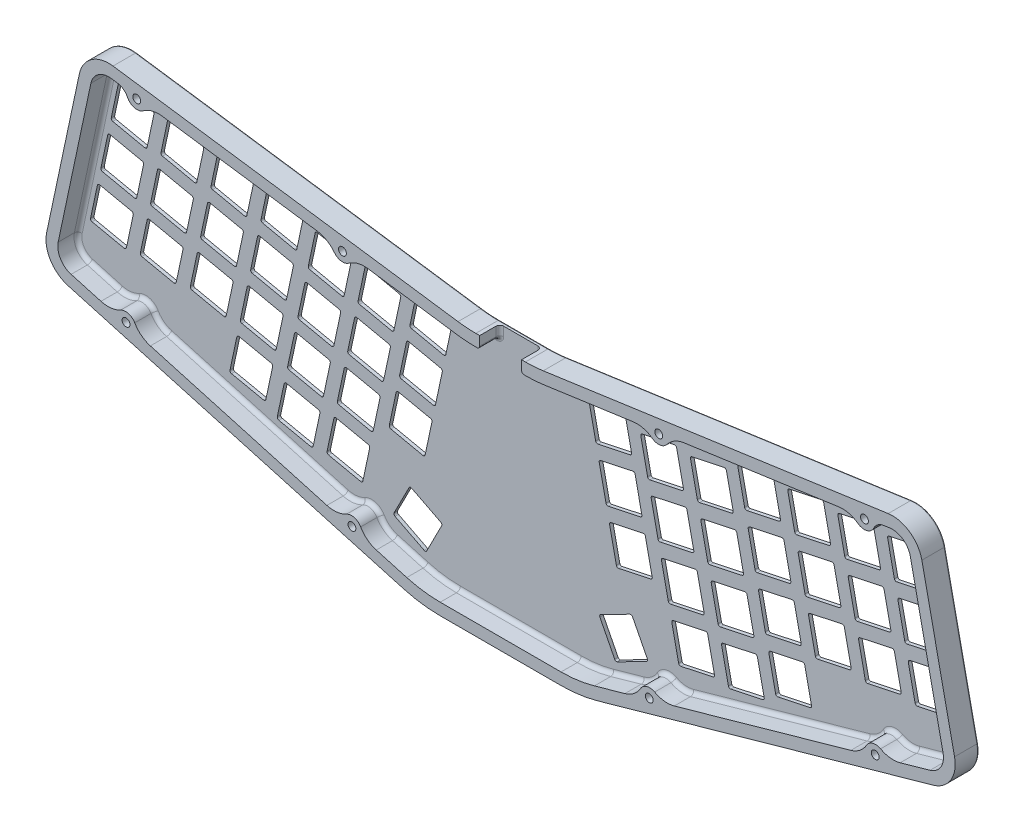
SolidWorks part; units mm, degrees
ref_plane "Front Plane" through (0, 0, 0) normal (0, 0, 1) x (1, 0, 0)
ref_plane "Top Plane" through (0, 0, 0) normal (0, 1, 0) x (1, 0, 0)
ref_plane "Right Plane" through (0, 0, 0) normal (1, 0, 0) x (0, 0, -1)
sketch "Model" plane through (0, 0, 0) normal (0, 0, 1) x (1, 0, 0)
  line L0 (7.1929, 63.9009) -> (19.4198, 61.302)
  line L1 (19.9974, 60.4125) -> (17.3986, 48.1856)
  line L2 (16.509, 47.6079) -> (4.2822, 50.2068)
  line L3 (3.7045, 51.0964) -> (6.3034, 63.3232)
  line L4 (3.2426, 45.3161) -> (15.4694, 42.7172)
  line L5 (16.0471, 41.8276) -> (13.4482, 29.6008)
  line L6 (12.5587, 29.0231) -> (0.3318, 31.622)
  line L7 (-0.2458, 32.5116) -> (2.3531, 44.7384)
  line L8 (-0.7077, 26.7313) -> (11.5191, 24.1324)
  line L9 (12.0968, 23.2428) -> (9.4979, 11.016)
  line L10 (8.6084, 10.4383) -> (-3.6185, 13.0372)
  line L11 (-4.1962, 13.9268) -> (-1.5973, 26.1536)
  line L12 (26.1936, 61.9069) -> (38.4204, 59.308)
  line L13 (38.9981, 58.4184) -> (36.3992, 46.1916)
  line L14 (35.5096, 45.6139) -> (23.2828, 48.2128)
  line L15 (22.7051, 49.1023) -> (25.304, 61.3292)
  line L16 (22.2432, 43.3221) -> (34.4701, 40.7232)
  line L17 (35.0478, 39.8336) -> (32.4489, 27.6068)
  line L18 (31.5593, 27.0291) -> (19.3325, 29.628)
  line L19 (18.7548, 30.5175) -> (21.3537, 42.7444)
  line L20 (18.2929, 24.7373) -> (30.5198, 22.1384)
  line L21 (31.0974, 21.2488) -> (28.4985, 9.022)
  line L22 (27.609, 8.4443) -> (15.3821, 11.0432)
  line L23 (14.8045, 11.9327) -> (17.4034, 24.1596)
  line L24 (45.2981, 60.4019) -> (57.525, 57.803)
  line L25 (58.1027, 56.9135) -> (55.5038, 44.6866)
  line L26 (54.6142, 44.109) -> (42.3874, 46.7078)
  line L27 (41.8097, 47.5974) -> (44.4086, 59.8242)
  line L28 (41.3478, 41.8171) -> (53.5747, 39.2182)
  line L29 (54.1523, 38.3287) -> (51.5534, 26.1018)
  line L30 (50.6639, 25.5241) -> (38.4371, 28.123)
  line L31 (37.8594, 29.0126) -> (40.4583, 41.2394)
  line L32 (37.3975, 23.2323) -> (49.6243, 20.6334)
  line L33 (50.202, 19.7439) -> (47.6031, 7.517)
  line L34 (46.7136, 6.9393) -> (34.4867, 9.5382)
  line L35 (33.9091, 10.4278) -> (36.5079, 22.6546)
  line L36 (64.4027, 58.897) -> (76.6296, 56.2981)
  line L37 (77.2072, 55.4085) -> (74.6083, 43.1817)
  line L38 (73.7188, 42.604) -> (61.492, 45.2029)
  line L39 (60.9143, 46.0924) -> (63.5132, 58.3193)
  line L40 (60.4524, 40.3122) -> (72.6792, 37.7133)
  line L41 (73.2569, 36.8237) -> (70.658, 24.5969)
  line L42 (69.7685, 24.0192) -> (57.5416, 26.6181)
  line L43 (56.964, 27.5076) -> (59.5629, 39.7345)
  line L44 (56.5021, 21.7274) -> (68.7289, 19.1285)
  line L45 (69.3066, 18.2389) -> (66.7077, 6.0121)
  line L46 (65.8182, 5.4344) -> (53.5913, 8.0333)
  line L47 (53.0136, 8.9228) -> (55.6125, 21.1497)
  line L48 (52.5518, 3.1425) -> (64.7786, 0.5437)
  line L49 (65.3563, -0.3459) -> (62.7574, -12.5727)
  line L50 (61.8678, -13.1504) -> (49.641, -10.5515)
  line L51 (49.0633, -9.662) -> (51.6622, 2.5649)
  line L52 (82.4677, 52.5013) -> (94.6946, 49.9024)
  line L53 (95.2723, 49.0128) -> (92.6734, 36.786)
  line L54 (91.7838, 36.2083) -> (79.557, 38.8072)
  line L55 (78.9793, 39.6967) -> (81.5782, 51.9236)
  line L56 (78.5174, 33.9165) -> (90.7443, 31.3176)
  line L57 (91.3219, 30.428) -> (88.723, 18.2012)
  line L58 (87.8335, 17.6235) -> (75.6067, 20.2224)
  line L59 (75.029, 21.1119) -> (77.6279, 33.3388)
  line L60 (74.5671, 15.3317) -> (86.7939, 12.7328)
  line L61 (87.3716, 11.8432) -> (84.7727, -0.3836)
  line L62 (83.8832, -0.9613) -> (71.6563, 1.6376)
  line L63 (71.0787, 2.5271) -> (73.6776, 14.754)
  line L64 (101.4684, 50.5072) -> (113.6952, 47.9083)
  line L65 (114.2729, 47.0188) -> (111.674, 34.792)
  line L66 (110.7845, 34.2143) -> (98.5576, 36.8132)
  line L67 (97.9799, 37.7027) -> (100.5788, 49.9296)
  line L68 (97.5181, 31.9224) -> (109.7449, 29.3235)
  line L69 (110.3226, 28.434) -> (107.7237, 16.2072)
  line L70 (106.8341, 15.6295) -> (94.6073, 18.2284)
  line L71 (94.0296, 19.1179) -> (96.6285, 31.3448)
  line L72 (93.5677, 13.3376) -> (105.7946, 10.7387)
  line L73 (106.3723, 9.8492) -> (103.7734, -2.3777)
  line L74 (102.8838, -2.9553) -> (90.657, -0.3564)
  line L75 (90.0793, 0.5331) -> (92.6782, 12.76)
  line L76 (134.1052, 48.9374) -> (131.5063, 36.7105)
  line L77 (130.6167, 36.1328) -> (118.3899, 38.7317)
  line L78 (117.8122, 39.6213) -> (120.4111, 51.8481)
  line L79 (117.3503, 33.841) -> (129.5772, 31.2421)
  line L80 (130.1548, 30.3526) -> (127.556, 18.1257)
  line L81 (126.6664, 17.548) -> (114.4396, 20.1469)
  line L82 (113.8619, 21.0365) -> (116.4608, 33.2633)
  line L83 (113.4, 15.2562) -> (125.6268, 12.6573)
  line L84 (126.2045, 11.7678) -> (123.6056, -0.4591)
  line L85 (122.7161, -1.0368) -> (110.4892, 1.5621)
  line L86 (109.9116, 2.4517) -> (112.5105, 14.6785)
  line L87 (70.6168, -3.2531) -> (82.8436, -5.852)
  line L88 (83.4213, -6.7416) -> (80.8224, -18.9684)
  line L89 (79.9329, -19.5461) -> (67.706, -16.9472)
  line L90 (67.1283, -16.0577) -> (69.7272, -3.8308)
  line L91 (89.6174, -5.2472) -> (101.8443, -7.8461)
  line L92 (102.4219, -8.7356) -> (99.823, -20.9625)
  line L93 (98.9335, -21.5401) -> (86.7066, -18.9412)
  line L94 (86.129, -18.0517) -> (88.7279, -5.8248)
  line L95 (117.654, -29.3648) -> (112.0852, -26.5274)
  line L96 (111.7574, -25.5186) -> (117.4323, -14.381)
  line L97 (118.4411, -14.0533) -> (129.5787, -19.7282)
  line L98 (129.9064, -20.7369) -> (124.2315, -31.8745)
  line L99 (123.2228, -32.2023) -> (117.654, -29.3648)
  line L100 (112.629, -33.5493) -> (124.2783, -36.8388)
  line L101 (137.0504, -38.6074) -> (160.1264, -38.6074)
  line L102 (160.1264, -38.6074) -> (183.2025, -38.6074)
  line L103 (195.9746, -36.8388) -> (207.6239, -33.5493)
  line L104 (226.4824, -28.2242) -> (271.949, -15.3856)
  line L105 (271.949, -15.3856) -> (293.9202, -9.1816)
  line L106 (210.7632, 57.9332) -> (177.0346, 53.1572)
  line L107 (169.604, 52.6338) -> (150.6488, 52.6338)
  line L108 (143.2182, 53.1572) -> (109.4896, 57.9332)
  line L109 (90.0873, 60.6806) -> (30.9176, 69.0589)
  line L110 (289.3352, 69.0589) -> (230.1656, 60.6806)
  line L111 (26.3327, -9.1816) -> (48.3039, -15.3856)
  line L112 (48.3039, -15.3856) -> (93.7705, -28.2242)
  line L113 (312.7787, -3.8564) -> (324.1811, -0.6367)
  line L114 (-2.1254, 39.3007) -> (3.622, 66.34)
  line L115 (-2.1254, 39.3007) -> (-8.8731, 7.5553)
  line L116 (13.8071, 71.4818) -> (11.4504, 71.8155)
  line L117 (-3.9283, -0.6367) -> (7.4742, -3.8564)
  line L118 (306.4458, 71.4818) -> (308.8024, 71.8155)
  line L119 (322.3782, 39.3007) -> (329.1259, 7.5553)
  line L120 (322.3782, 39.3007) -> (316.6308, 66.34)
  line L121 (121.3006, 52.4258) -> (133.5275, 49.8269)
  line L122 (313.0599, 63.9009) -> (300.8331, 61.302)
  line L123 (300.2554, 60.4125) -> (302.8543, 48.1856)
  line L124 (303.7438, 47.6079) -> (315.9707, 50.2068)
  line L125 (316.5483, 51.0964) -> (313.9494, 63.3232)
  line L126 (317.0102, 45.3161) -> (304.7834, 42.7172)
  line L127 (304.2057, 41.8276) -> (306.8046, 29.6008)
  line L128 (307.6941, 29.0231) -> (319.921, 31.622)
  line L129 (320.4987, 32.5116) -> (317.8998, 44.7384)
  line L130 (320.9605, 26.7313) -> (308.7337, 24.1324)
  line L131 (308.156, 23.2428) -> (310.7549, 11.016)
  line L132 (311.6445, 10.4383) -> (323.8713, 13.0372)
  line L133 (324.449, 13.9268) -> (321.8501, 26.1536)
  line L134 (294.0593, 61.9069) -> (281.8324, 59.308)
  line L135 (281.2548, 58.4184) -> (283.8536, 46.1916)
  line L136 (284.7432, 45.6139) -> (296.97, 48.2128)
  line L137 (297.5477, 49.1023) -> (294.9488, 61.3292)
  line L138 (298.0096, 43.3221) -> (285.7828, 40.7232)
  line L139 (285.2051, 39.8336) -> (287.804, 27.6068)
  line L140 (288.6935, 27.0291) -> (300.9204, 29.628)
  line L141 (301.498, 30.5175) -> (298.8991, 42.7444)
  line L142 (301.9599, 24.7373) -> (289.7331, 22.1384)
  line L143 (289.1554, 21.2488) -> (291.7543, 9.022)
  line L144 (292.6438, 8.4443) -> (304.8707, 11.0432)
  line L145 (305.4484, 11.9327) -> (302.8495, 24.1596)
  line L146 (274.9547, 60.4019) -> (262.7278, 57.803)
  line L147 (262.1502, 56.9135) -> (264.7491, 44.6866)
  line L148 (265.6386, 44.109) -> (277.8655, 46.7078)
  line L149 (278.4431, 47.5974) -> (275.8442, 59.8242)
  line L150 (278.905, 41.8171) -> (266.6782, 39.2182)
  line L151 (266.1005, 38.3287) -> (268.6994, 26.1018)
  line L152 (269.5889, 25.5241) -> (281.8158, 28.123)
  line L153 (282.3935, 29.0126) -> (279.7946, 41.2394)
  line L154 (282.8553, 23.2323) -> (270.6285, 20.6334)
  line L155 (270.0508, 19.7439) -> (272.6497, 7.517)
  line L156 (273.5393, 6.9393) -> (285.7661, 9.5382)
  line L157 (286.3438, 10.4278) -> (283.7449, 22.6546)
  line L158 (255.8501, 58.897) -> (243.6233, 56.2981)
  line L159 (243.0456, 55.4085) -> (245.6445, 43.1817)
  line L160 (246.534, 42.604) -> (258.7609, 45.2029)
  line L161 (259.3385, 46.0924) -> (256.7397, 58.3193)
  line L162 (259.8004, 40.3122) -> (247.5736, 37.7133)
  line L163 (246.9959, 36.8237) -> (249.5948, 24.5969)
  line L164 (250.4843, 24.0192) -> (262.7112, 26.6181)
  line L165 (263.2889, 27.5076) -> (260.69, 39.7345)
  line L166 (263.7508, 21.7274) -> (251.5239, 19.1285)
  line L167 (250.9462, 18.2389) -> (253.5451, 6.0121)
  line L168 (254.4347, 5.4344) -> (266.6615, 8.0333)
  line L169 (267.2392, 8.9228) -> (264.6403, 21.1497)
  line L170 (267.7011, 3.1425) -> (255.4742, 0.5437)
  line L171 (254.8966, -0.3459) -> (257.4954, -12.5727)
  line L172 (258.385, -13.1504) -> (270.6118, -10.5515)
  line L173 (271.1895, -9.662) -> (268.5906, 2.5649)
  line L174 (237.7851, 52.5013) -> (225.5582, 49.9024)
  line L175 (224.9806, 49.0128) -> (227.5795, 36.786)
  line L176 (228.469, 36.2083) -> (240.6958, 38.8072)
  line L177 (241.2735, 39.6967) -> (238.6746, 51.9236)
  line L178 (241.7354, 33.9165) -> (229.5086, 31.3176)
  line L179 (228.9309, 30.428) -> (231.5298, 18.2012)
  line L180 (232.4193, 17.6235) -> (244.6462, 20.2224)
  line L181 (245.2238, 21.1119) -> (242.6249, 33.3388)
  line L182 (245.6857, 15.3317) -> (233.4589, 12.7328)
  line L183 (232.8812, 11.8432) -> (235.4801, -0.3836)
  line L184 (236.3696, -0.9613) -> (248.5965, 1.6376)
  line L185 (249.1742, 2.5271) -> (246.5753, 14.754)
  line L186 (218.7845, 50.5072) -> (206.5576, 47.9083)
  line L187 (205.9799, 47.0188) -> (208.5788, 34.792)
  line L188 (209.4684, 34.2143) -> (221.6952, 36.8132)
  line L189 (222.2729, 37.7027) -> (219.674, 49.9296)
  line L190 (222.7348, 31.9224) -> (210.5079, 29.3235)
  line L191 (209.9303, 28.434) -> (212.5292, 16.2072)
  line L192 (213.4187, 15.6295) -> (225.6455, 18.2284)
  line L193 (226.2232, 19.1179) -> (223.6243, 31.3448)
  line L194 (226.6851, 13.3376) -> (214.4583, 10.7387)
  line L195 (213.8806, 9.8492) -> (216.4795, -2.3777)
  line L196 (217.369, -2.9553) -> (229.5959, -0.3564)
  line L197 (230.1735, 0.5331) -> (227.5746, 12.76)
  line L198 (186.1477, 48.9374) -> (188.7466, 36.7105)
  line L199 (189.6361, 36.1328) -> (201.8629, 38.7317)
  line L200 (202.4406, 39.6213) -> (199.8417, 51.8481)
  line L201 (202.9025, 33.841) -> (190.6757, 31.2421)
  line L202 (190.098, 30.3526) -> (192.6969, 18.1257)
  line L203 (193.5864, 17.548) -> (205.8133, 20.1469)
  line L204 (206.3909, 21.0365) -> (203.792, 33.2633)
  line L205 (206.8528, 15.2562) -> (194.626, 12.6573)
  line L206 (194.0483, 11.7678) -> (196.6472, -0.4591)
  line L207 (197.5367, -1.0368) -> (209.7636, 1.5621)
  line L208 (210.3413, 2.4517) -> (207.7424, 14.6785)
  line L209 (249.636, -3.2531) -> (237.4092, -5.852)
  line L210 (236.8315, -6.7416) -> (239.4304, -18.9684)
  line L211 (240.32, -19.5461) -> (252.5468, -16.9472)
  line L212 (253.1245, -16.0577) -> (250.5256, -3.8308)
  line L213 (230.6354, -5.2472) -> (218.4086, -7.8461)
  line L214 (217.8309, -8.7356) -> (220.4298, -20.9625)
  line L215 (221.3193, -21.5401) -> (233.5462, -18.9412)
  line L216 (234.1239, -18.0517) -> (231.525, -5.8248)
  line L217 (202.5988, -29.3648) -> (208.1676, -26.5274)
  line L218 (208.4954, -25.5186) -> (202.8205, -14.381)
  line L219 (201.8118, -14.0533) -> (190.6742, -19.7282)
  line L220 (190.3464, -20.7369) -> (196.0213, -31.8745)
  line L221 (197.03, -32.2023) -> (202.5988, -29.3648)
  line L222 (198.9522, 52.4258) -> (186.7253, 49.8269)
  line L223 (169.604, 55.6338) -> (150.6488, 55.6338)
  line L224 (143.6388, 56.1276) -> (11.8711, 74.7858)
  line L225 (0.6876, 66.9637) -> (-5.0598, 39.9244)
  line L226 (-5.0598, 39.9244) -> (-11.8075, 8.179)
  line L227 (-4.7435, -3.5238) -> (47.4886, -18.2727)
  line L228 (47.4886, -18.2727) -> (123.463, -39.7259)
  line L229 (137.0504, -41.6074) -> (160.1264, -41.6074)
  line L230 (160.1264, -41.6074) -> (183.2025, -41.6074)
  line L231 (196.7898, -39.7259) -> (272.7642, -18.2727)
  line L232 (272.7642, -18.2727) -> (324.9963, -3.5238)
  line L233 (332.0603, 8.179) -> (325.3126, 39.9244)
  line L234 (325.3126, 39.9244) -> (319.5653, 66.9637)
  line L235 (308.3818, 74.7858) -> (176.614, 56.1276)
  line L236 (169.604, 57.1338) -> (150.6488, 57.1338)
  line L237 (143.8491, 57.6128) -> (12.0814, 76.271)
  line L238 (-0.7797, 67.2756) -> (-6.527, 40.2363)
  line L239 (-6.527, 40.2363) -> (-13.2747, 8.4909)
  line L240 (-5.1511, -4.9673) -> (47.081, -19.7163)
  line L241 (47.081, -19.7163) -> (123.0554, -41.1694)
  line L242 (137.0504, -43.1074) -> (160.1264, -43.1074)
  line L243 (160.1264, -43.1074) -> (183.2025, -43.1074)
  line L244 (197.1974, -41.1694) -> (273.1718, -19.7163)
  line L245 (273.1718, -19.7163) -> (325.404, -4.9673)
  line L246 (333.5276, 8.4909) -> (326.7799, 40.2363)
  line L247 (326.7799, 40.2363) -> (321.0325, 67.2756)
  line L248 (308.1715, 76.271) -> (176.4037, 57.6128)
  arc A0 (106.6702, -28.8979) -> (101.2821, -27.3764) centre (103.1997, -30.8868) ccw
  arc A1 (93.7705, -28.2242) -> (101.2821, -27.3764) centre (96.4879, -18.6005) ccw
  arc A2 (106.6702, -28.8979) -> (112.629, -33.5493) centre (115.3464, -23.9256) ccw
  circle A3 centre (103.3356, -30.4056) radius 1.5
  arc A4 (207.6239, -33.5493) -> (213.5826, -28.8979) centre (204.9064, -23.9256) ccw
  arc A5 (218.9708, -27.3764) -> (226.4824, -28.2242) centre (223.7649, -18.6005) ccw
  arc A6 (218.9708, -27.3764) -> (213.5826, -28.8979) centre (217.0531, -30.8868) ccw
  circle A7 centre (216.9173, -30.4056) radius 1.5
  arc A8 (218.0932, 56.0855) -> (223.6367, 56.8704) centre (220.4644, 59.3069) ccw
  arc A9 (96.6161, 56.8704) -> (102.1596, 56.0855) centre (99.7884, 59.3069) ccw
  arc A10 (109.4896, 57.9332) -> (102.1596, 56.0855) centre (108.0876, 48.032) ccw
  arc A11 (96.6161, 56.8704) -> (90.0873, 60.6806) centre (88.6852, 50.7793) ccw
  arc A12 (218.0932, 56.0855) -> (210.7632, 57.9332) centre (212.1652, 48.032) ccw
  arc A13 (230.1656, 60.6806) -> (223.6367, 56.8704) centre (231.5676, 50.7793) ccw
  circle A14 centre (99.7183, 58.8118) radius 1.5
  circle A15 centre (220.5345, 58.8118) radius 1.5
  arc A16 (305.2671, -3.0086) -> (299.8789, -4.5301) centre (303.3494, -6.519) ccw
  arc A17 (20.3739, -4.5301) -> (14.9858, -3.0086) centre (16.9034, -6.519) ccw
  arc A18 (20.3739, -4.5301) -> (26.3327, -9.1816) centre (29.0501, 0.4421) ccw
  arc A19 (305.2671, -3.0086) -> (312.7787, -3.8564) centre (310.0612, 5.7673) ccw
  arc A20 (293.9202, -9.1816) -> (299.8789, -4.5301) centre (291.2027, 0.4421) ccw
  arc A21 (7.4742, -3.8564) -> (14.9858, -3.0086) centre (10.1916, 5.7673) ccw
  circle A22 centre (17.0393, -6.0378) radius 1.5
  circle A23 centre (303.2135, -6.0378) radius 1.5
  arc A24 (-8.8731, 7.5553) -> (-3.9283, -0.6367) centre (-2.026, 6.0999) ccw
  arc A25 (11.4504, 71.8155) -> (3.622, 66.34) centre (10.469, 64.8846) ccw
  arc A26 (316.6308, 66.34) -> (308.8024, 71.8155) centre (309.7838, 64.8846) ccw
  arc A27 (324.1811, -0.6367) -> (329.1259, 7.5553) centre (322.2789, 6.0999) ccw
  arc A28 (296.6652, 67.2112) -> (302.641, 68.6986) centre (299.0364, 70.4326) ccw
  arc A29 (17.6118, 68.6986) -> (23.5876, 67.2112) centre (21.2165, 70.4326) ccw
  arc A30 (30.9176, 69.0589) -> (23.5876, 67.2112) centre (29.5156, 59.1577) ccw
  arc A31 (17.6118, 68.6986) -> (13.8071, 71.4818) centre (13.106, 66.5312) ccw
  arc A32 (306.4458, 71.4818) -> (302.641, 68.6986) centre (307.1468, 66.5312) ccw
  arc A33 (296.6652, 67.2112) -> (289.3352, 69.0589) centre (290.7372, 59.1577) ccw
  circle A34 centre (299.1065, 69.9376) radius 1.5
  circle A35 centre (21.1464, 69.9376) radius 1.5
  arc A36 (3.7045, 51.0964) -> (4.2822, 50.2068) centre (4.4381, 50.9404) ccw
  arc A37 (7.1929, 63.9009) -> (6.3034, 63.3232) centre (7.037, 63.1673) ccw
  arc A38 (19.9974, 60.4125) -> (19.4198, 61.302) centre (19.2638, 60.5684) ccw
  arc A39 (16.509, 47.6079) -> (17.3986, 48.1856) centre (16.6649, 48.3415) ccw
  arc A40 (3.2426, 45.3161) -> (2.3531, 44.7384) centre (3.0867, 44.5825) ccw
  arc A41 (-0.2458, 32.5116) -> (0.3318, 31.622) centre (0.4878, 32.3556) ccw
  arc A42 (12.5587, 29.0231) -> (13.4482, 29.6008) centre (12.7146, 29.7567) ccw
  arc A43 (16.0471, 41.8276) -> (15.4694, 42.7172) centre (15.3135, 41.9836) ccw
  arc A44 (-0.7077, 26.7313) -> (-1.5973, 26.1536) centre (-0.8637, 25.9977) ccw
  arc A45 (-4.1962, 13.9268) -> (-3.6185, 13.0372) centre (-3.4625, 13.7708) ccw
  arc A46 (8.6084, 10.4383) -> (9.4979, 11.016) centre (8.7643, 11.1719) ccw
  arc A47 (12.0968, 23.2428) -> (11.5191, 24.1324) centre (11.3632, 23.3988) ccw
  arc A48 (14.8045, 11.9327) -> (15.3821, 11.0432) centre (15.5381, 11.7768) ccw
  arc A49 (27.609, 8.4443) -> (28.4985, 9.022) centre (27.7649, 9.1779) ccw
  arc A50 (31.0974, 21.2488) -> (30.5198, 22.1384) centre (30.3638, 21.4048) ccw
  arc A51 (18.2929, 24.7373) -> (17.4034, 24.1596) centre (18.137, 24.0036) ccw
  arc A52 (18.7548, 30.5175) -> (19.3325, 29.628) centre (19.4884, 30.3616) ccw
  arc A53 (31.5593, 27.0291) -> (32.4489, 27.6068) centre (31.7152, 27.7627) ccw
  arc A54 (35.0478, 39.8336) -> (34.4701, 40.7232) centre (34.3141, 39.9896) ccw
  arc A55 (22.2432, 43.3221) -> (21.3537, 42.7444) centre (22.0873, 42.5885) ccw
  arc A56 (22.7051, 49.1023) -> (23.2828, 48.2128) centre (23.4387, 48.9464) ccw
  arc A57 (35.5096, 45.6139) -> (36.3992, 46.1916) centre (35.6656, 46.3475) ccw
  arc A58 (38.9981, 58.4184) -> (38.4204, 59.308) centre (38.2645, 58.5744) ccw
  arc A59 (26.1936, 61.9069) -> (25.304, 61.3292) centre (26.0376, 61.1733) ccw
  arc A60 (33.9091, 10.4278) -> (34.4867, 9.5382) centre (34.6427, 10.2718) ccw
  arc A61 (37.3975, 23.2323) -> (36.5079, 22.6546) centre (37.2416, 22.4987) ccw
  arc A62 (50.202, 19.7439) -> (49.6243, 20.6334) centre (49.4684, 19.8998) ccw
  arc A63 (46.7136, 6.9393) -> (47.6031, 7.517) centre (46.8695, 7.673) ccw
  arc A64 (50.6639, 25.5241) -> (51.5534, 26.1018) centre (50.8198, 26.2578) ccw
  arc A65 (37.8594, 29.0126) -> (38.4371, 28.123) centre (38.593, 28.8567) ccw
  arc A66 (41.3478, 41.8171) -> (40.4583, 41.2394) centre (41.1919, 41.0835) ccw
  arc A67 (54.1523, 38.3287) -> (53.5747, 39.2182) centre (53.4187, 38.4846) ccw
  arc A68 (54.6142, 44.109) -> (55.5038, 44.6866) centre (54.7702, 44.8426) ccw
  arc A69 (41.8097, 47.5974) -> (42.3874, 46.7078) centre (42.5433, 47.4415) ccw
  arc A70 (45.2981, 60.4019) -> (44.4086, 59.8242) centre (45.1422, 59.6683) ccw
  arc A71 (58.1027, 56.9135) -> (57.525, 57.803) centre (57.369, 57.0694) ccw
  arc A72 (56.964, 27.5076) -> (57.5416, 26.6181) centre (57.6976, 27.3517) ccw
  arc A73 (60.4524, 40.3122) -> (59.5629, 39.7345) centre (60.2965, 39.5785) ccw
  arc A74 (73.2569, 36.8237) -> (72.6792, 37.7133) centre (72.5233, 36.9797) ccw
  arc A75 (69.7685, 24.0192) -> (70.658, 24.5969) centre (69.9244, 24.7528) ccw
  arc A76 (60.9143, 46.0924) -> (61.492, 45.2029) centre (61.6479, 45.9365) ccw
  arc A77 (73.7188, 42.604) -> (74.6083, 43.1817) centre (73.8747, 43.3376) ccw
  arc A78 (77.2072, 55.4085) -> (76.6296, 56.2981) centre (76.4736, 55.5645) ccw
  arc A79 (64.4027, 58.897) -> (63.5132, 58.3193) centre (64.2468, 58.1634) ccw
  arc A80 (53.0136, 8.9228) -> (53.5913, 8.0333) centre (53.7472, 8.7669) ccw
  arc A81 (56.5021, 21.7274) -> (55.6125, 21.1497) centre (56.3461, 20.9937) ccw
  arc A82 (69.3066, 18.2389) -> (68.7289, 19.1285) centre (68.573, 18.3948) ccw
  arc A83 (65.8182, 5.4344) -> (66.7077, 6.0121) centre (65.9741, 6.168) ccw
  arc A84 (49.0633, -9.662) -> (49.641, -10.5515) centre (49.7969, -9.8179) ccw
  arc A85 (52.5518, 3.1425) -> (51.6622, 2.5649) centre (52.3958, 2.4089) ccw
  arc A86 (65.3563, -0.3459) -> (64.7786, 0.5437) centre (64.6227, -0.19) ccw
  arc A87 (61.8678, -13.1504) -> (62.7574, -12.5727) centre (62.0238, -12.4168) ccw
  arc A88 (67.1283, -16.0577) -> (67.706, -16.9472) centre (67.8619, -16.2136) ccw
  arc A89 (70.6168, -3.2531) -> (69.7272, -3.8308) centre (70.4608, -3.9868) ccw
  arc A90 (83.4213, -6.7416) -> (82.8436, -5.852) centre (82.6877, -6.5856) ccw
  arc A91 (79.9329, -19.5461) -> (80.8224, -18.9684) centre (80.0888, -18.8125) ccw
  arc A92 (71.0787, 2.5271) -> (71.6563, 1.6376) centre (71.8123, 2.3712) ccw
  arc A93 (83.8832, -0.9613) -> (84.7727, -0.3836) centre (84.0391, -0.2277) ccw
  arc A94 (87.3716, 11.8432) -> (86.7939, 12.7328) centre (86.638, 11.9992) ccw
  arc A95 (74.5671, 15.3317) -> (73.6776, 14.754) centre (74.4112, 14.5981) ccw
  arc A96 (75.029, 21.1119) -> (75.6067, 20.2224) centre (75.7626, 20.956) ccw
  arc A97 (87.8335, 17.6235) -> (88.723, 18.2012) centre (87.9894, 18.3571) ccw
  arc A98 (91.3219, 30.428) -> (90.7443, 31.3176) centre (90.5883, 30.584) ccw
  arc A99 (78.5174, 33.9165) -> (77.6279, 33.3388) centre (78.3615, 33.1829) ccw
  arc A100 (78.9793, 39.6967) -> (79.557, 38.8072) centre (79.7129, 39.5408) ccw
  arc A101 (82.4677, 52.5013) -> (81.5782, 51.9236) centre (82.3118, 51.7677) ccw
  arc A102 (95.2723, 49.0128) -> (94.6946, 49.9024) centre (94.5387, 49.1688) ccw
  arc A103 (91.7838, 36.2083) -> (92.6734, 36.786) centre (91.9398, 36.9419) ccw
  arc A104 (97.9799, 37.7027) -> (98.5576, 36.8132) centre (98.7135, 37.5468) ccw
  arc A105 (101.4684, 50.5072) -> (100.5788, 49.9296) centre (101.3124, 49.7736) ccw
  arc A106 (114.2729, 47.0188) -> (113.6952, 47.9083) centre (113.5393, 47.1747) ccw
  arc A107 (110.7845, 34.2143) -> (111.674, 34.792) centre (110.9404, 34.9479) ccw
  arc A108 (97.5181, 31.9224) -> (96.6285, 31.3448) centre (97.3621, 31.1888) ccw
  arc A109 (110.3226, 28.434) -> (109.7449, 29.3235) centre (109.589, 28.5899) ccw
  arc A110 (106.8341, 15.6295) -> (107.7237, 16.2072) centre (106.9901, 16.3631) ccw
  arc A111 (94.0296, 19.1179) -> (94.6073, 18.2284) centre (94.7632, 18.962) ccw
  arc A112 (93.5677, 13.3376) -> (92.6782, 12.76) centre (93.4118, 12.604) ccw
  arc A113 (106.3723, 9.8492) -> (105.7946, 10.7387) centre (105.6386, 10.0051) ccw
  arc A114 (102.8838, -2.9553) -> (103.7734, -2.3777) centre (103.0397, -2.2217) ccw
  arc A115 (90.0793, 0.5331) -> (90.657, -0.3564) centre (90.8129, 0.3772) ccw
  arc A116 (89.6174, -5.2472) -> (88.7279, -5.8248) centre (89.4615, -5.9808) ccw
  arc A117 (102.4219, -8.7356) -> (101.8443, -7.8461) centre (101.6883, -8.5797) ccw
  arc A118 (98.9335, -21.5401) -> (99.823, -20.9625) centre (99.0894, -20.8065) ccw
  arc A119 (86.129, -18.0517) -> (86.7066, -18.9412) centre (86.8626, -18.2076) ccw
  arc A120 (111.7574, -25.5186) -> (112.0852, -26.5274) centre (112.4257, -25.8591) ccw
  arc A121 (118.4411, -14.0533) -> (117.4323, -14.381) centre (118.1006, -14.7215) ccw
  arc A122 (129.9064, -20.7369) -> (129.5787, -19.7282) centre (129.2382, -20.3964) ccw
  arc A123 (123.2228, -32.2023) -> (124.2315, -31.8745) centre (123.5633, -31.534) ccw
  arc A124 (109.9116, 2.4517) -> (110.4892, 1.5621) centre (110.6452, 2.2957) ccw
  arc A125 (122.7161, -1.0368) -> (123.6056, -0.4591) centre (122.872, -0.3032) ccw
  arc A126 (126.2045, 11.7678) -> (125.6268, 12.6573) centre (125.4709, 11.9237) ccw
  arc A127 (113.4, 15.2562) -> (112.5105, 14.6785) centre (113.2441, 14.5226) ccw
  arc A128 (113.8619, 21.0365) -> (114.4396, 20.1469) centre (114.5955, 20.8805) ccw
  arc A129 (126.6664, 17.548) -> (127.556, 18.1257) centre (126.8223, 18.2817) ccw
  arc A130 (130.1548, 30.3526) -> (129.5772, 31.2421) centre (129.4212, 30.5085) ccw
  arc A131 (117.3503, 33.841) -> (116.4608, 33.2633) centre (117.1944, 33.1074) ccw
  arc A132 (117.8122, 39.6213) -> (118.3899, 38.7317) centre (118.5458, 39.4654) ccw
  arc A133 (130.6167, 36.1328) -> (131.5063, 36.7105) centre (130.7727, 36.8665) ccw
  arc A134 (134.1052, 48.9374) -> (133.5275, 49.8269) centre (133.3716, 49.0933) ccw
  arc A135 (121.3006, 52.4258) -> (120.4111, 51.8481) centre (121.1447, 51.6922) ccw
  arc A136 (313.9494, 63.3232) -> (313.0599, 63.9009) centre (313.2158, 63.1673) ccw
  arc A137 (300.8331, 61.302) -> (300.2554, 60.4125) centre (300.989, 60.5684) ccw
  arc A138 (302.8543, 48.1856) -> (303.7438, 47.6079) centre (303.5879, 48.3415) ccw
  arc A139 (315.9707, 50.2068) -> (316.5483, 51.0964) centre (315.8147, 50.9404) ccw
  arc A140 (317.8998, 44.7384) -> (317.0102, 45.3161) centre (317.1662, 44.5825) ccw
  arc A141 (304.7834, 42.7172) -> (304.2057, 41.8276) centre (304.9393, 41.9836) ccw
  arc A142 (306.8046, 29.6008) -> (307.6941, 29.0231) centre (307.5382, 29.7567) ccw
  arc A143 (319.921, 31.622) -> (320.4987, 32.5116) centre (319.7651, 32.3556) ccw
  arc A144 (321.8501, 26.1536) -> (320.9605, 26.7313) centre (321.1165, 25.9977) ccw
  arc A145 (308.7337, 24.1324) -> (308.156, 23.2428) centre (308.8896, 23.3988) ccw
  arc A146 (310.7549, 11.016) -> (311.6445, 10.4383) centre (311.4885, 11.1719) ccw
  arc A147 (323.8713, 13.0372) -> (324.449, 13.9268) centre (323.7154, 13.7708) ccw
  arc A148 (294.9488, 61.3292) -> (294.0593, 61.9069) centre (294.2152, 61.1733) ccw
  arc A149 (281.8324, 59.308) -> (281.2548, 58.4184) centre (281.9884, 58.5744) ccw
  arc A150 (283.8536, 46.1916) -> (284.7432, 45.6139) centre (284.5873, 46.3475) ccw
  arc A151 (296.97, 48.2128) -> (297.5477, 49.1023) centre (296.8141, 48.9464) ccw
  arc A152 (298.8991, 42.7444) -> (298.0096, 43.3221) centre (298.1655, 42.5885) ccw
  arc A153 (285.7828, 40.7232) -> (285.2051, 39.8336) centre (285.9387, 39.9896) ccw
  arc A154 (287.804, 27.6068) -> (288.6935, 27.0291) centre (288.5376, 27.7627) ccw
  arc A155 (300.9204, 29.628) -> (301.498, 30.5175) centre (300.7644, 30.3616) ccw
  arc A156 (302.8495, 24.1596) -> (301.9599, 24.7373) centre (302.1159, 24.0036) ccw
  arc A157 (289.7331, 22.1384) -> (289.1554, 21.2488) centre (289.889, 21.4048) ccw
  arc A158 (291.7543, 9.022) -> (292.6438, 8.4443) centre (292.4879, 9.1779) ccw
  arc A159 (304.8707, 11.0432) -> (305.4484, 11.9327) centre (304.7147, 11.7768) ccw
  arc A160 (262.7278, 57.803) -> (262.1502, 56.9135) centre (262.8838, 57.0694) ccw
  arc A161 (275.8442, 59.8242) -> (274.9547, 60.4019) centre (275.1106, 59.6683) ccw
  arc A162 (264.7491, 44.6866) -> (265.6386, 44.109) centre (265.4827, 44.8426) ccw
  arc A163 (277.8655, 46.7078) -> (278.4431, 47.5974) centre (277.7095, 47.4415) ccw
  arc A164 (266.6782, 39.2182) -> (266.1005, 38.3287) centre (266.8341, 38.4846) ccw
  arc A165 (279.7946, 41.2394) -> (278.905, 41.8171) centre (279.0609, 41.0835) ccw
  arc A166 (268.6994, 26.1018) -> (269.5889, 25.5241) centre (269.433, 26.2578) ccw
  arc A167 (281.8158, 28.123) -> (282.3935, 29.0126) centre (281.6598, 28.8567) ccw
  arc A168 (270.6285, 20.6334) -> (270.0508, 19.7439) centre (270.7844, 19.8998) ccw
  arc A169 (283.7449, 22.6546) -> (282.8553, 23.2323) centre (283.0113, 22.4987) ccw
  arc A170 (272.6497, 7.517) -> (273.5393, 6.9393) centre (273.3833, 7.673) ccw
  arc A171 (285.7661, 9.5382) -> (286.3438, 10.4278) centre (285.6102, 10.2718) ccw
  arc A172 (256.7397, 58.3193) -> (255.8501, 58.897) centre (256.006, 58.1634) ccw
  arc A173 (243.6233, 56.2981) -> (243.0456, 55.4085) centre (243.7792, 55.5645) ccw
  arc A174 (245.6445, 43.1817) -> (246.534, 42.604) centre (246.3781, 43.3376) ccw
  arc A175 (258.7609, 45.2029) -> (259.3385, 46.0924) centre (258.6049, 45.9365) ccw
  arc A176 (247.5736, 37.7133) -> (246.9959, 36.8237) centre (247.7295, 36.9797) ccw
  arc A177 (260.69, 39.7345) -> (259.8004, 40.3122) centre (259.9564, 39.5785) ccw
  arc A178 (249.5948, 24.5969) -> (250.4843, 24.0192) centre (250.3284, 24.7528) ccw
  arc A179 (262.7112, 26.6181) -> (263.2889, 27.5076) centre (262.5553, 27.3517) ccw
  arc A180 (251.5239, 19.1285) -> (250.9462, 18.2389) centre (251.6798, 18.3948) ccw
  arc A181 (253.5451, 6.0121) -> (254.4347, 5.4344) centre (254.2787, 6.168) ccw
  arc A182 (264.6403, 21.1497) -> (263.7508, 21.7274) centre (263.9067, 20.9937) ccw
  arc A183 (266.6615, 8.0333) -> (267.2392, 8.9228) centre (266.5056, 8.7669) ccw
  arc A184 (255.4742, 0.5437) -> (254.8966, -0.3459) centre (255.6302, -0.19) ccw
  arc A185 (257.4954, -12.5727) -> (258.385, -13.1504) centre (258.2291, -12.4168) ccw
  arc A186 (268.5906, 2.5649) -> (267.7011, 3.1425) centre (267.857, 2.4089) ccw
  arc A187 (270.6118, -10.5515) -> (271.1895, -9.662) centre (270.4559, -9.8179) ccw
  arc A188 (225.5582, 49.9024) -> (224.9806, 49.0128) centre (225.7142, 49.1688) ccw
  arc A189 (238.6746, 51.9236) -> (237.7851, 52.5013) centre (237.941, 51.7677) ccw
  arc A190 (227.5795, 36.786) -> (228.469, 36.2083) centre (228.3131, 36.9419) ccw
  arc A191 (240.6958, 38.8072) -> (241.2735, 39.6967) centre (240.5399, 39.5408) ccw
  arc A192 (242.6249, 33.3388) -> (241.7354, 33.9165) centre (241.8913, 33.1829) ccw
  arc A193 (229.5086, 31.3176) -> (228.9309, 30.428) centre (229.6645, 30.584) ccw
  arc A194 (231.5298, 18.2012) -> (232.4193, 17.6235) centre (232.2634, 18.3571) ccw
  arc A195 (244.6462, 20.2224) -> (245.2238, 21.1119) centre (244.4902, 20.956) ccw
  arc A196 (246.5753, 14.754) -> (245.6857, 15.3317) centre (245.8417, 14.5981) ccw
  arc A197 (233.4589, 12.7328) -> (232.8812, 11.8432) centre (233.6148, 11.9992) ccw
  arc A198 (235.4801, -0.3836) -> (236.3696, -0.9613) centre (236.2137, -0.2277) ccw
  arc A199 (248.5965, 1.6376) -> (249.1742, 2.5271) centre (248.4406, 2.3712) ccw
  arc A200 (206.5576, 47.9083) -> (205.9799, 47.0188) centre (206.7135, 47.1747) ccw
  arc A201 (219.674, 49.9296) -> (218.7845, 50.5072) centre (218.9404, 49.7736) ccw
  arc A202 (208.5788, 34.792) -> (209.4684, 34.2143) centre (209.3124, 34.9479) ccw
  arc A203 (221.6952, 36.8132) -> (222.2729, 37.7027) centre (221.5393, 37.5468) ccw
  arc A204 (210.5079, 29.3235) -> (209.9303, 28.434) centre (210.6639, 28.5899) ccw
  arc A205 (223.6243, 31.3448) -> (222.7348, 31.9224) centre (222.8907, 31.1888) ccw
  arc A206 (212.5292, 16.2072) -> (213.4187, 15.6295) centre (213.2628, 16.3631) ccw
  arc A207 (225.6455, 18.2284) -> (226.2232, 19.1179) centre (225.4896, 18.962) ccw
  arc A208 (227.5746, 12.76) -> (226.6851, 13.3376) centre (226.841, 12.604) ccw
  arc A209 (216.4795, -2.3777) -> (217.369, -2.9553) centre (217.2131, -2.2217) ccw
  arc A210 (214.4583, 10.7387) -> (213.8806, 9.8492) centre (214.6142, 10.0051) ccw
  arc A211 (229.5959, -0.3564) -> (230.1735, 0.5331) centre (229.4399, 0.3772) ccw
  arc A212 (199.8417, 51.8481) -> (198.9522, 52.4258) centre (199.1081, 51.6922) ccw
  arc A213 (186.7253, 49.8269) -> (186.1477, 48.9374) centre (186.8813, 49.0933) ccw
  arc A214 (188.7466, 36.7105) -> (189.6361, 36.1328) centre (189.4802, 36.8665) ccw
  arc A215 (201.8629, 38.7317) -> (202.4406, 39.6213) centre (201.707, 39.4654) ccw
  arc A216 (203.792, 33.2633) -> (202.9025, 33.841) centre (203.0584, 33.1074) ccw
  arc A217 (190.6757, 31.2421) -> (190.098, 30.3526) centre (190.8316, 30.5085) ccw
  arc A218 (192.6969, 18.1257) -> (193.5864, 17.548) centre (193.4305, 18.2817) ccw
  arc A219 (205.8133, 20.1469) -> (206.3909, 21.0365) centre (205.6573, 20.8805) ccw
  arc A220 (207.7424, 14.6785) -> (206.8528, 15.2562) centre (207.0088, 14.5226) ccw
  arc A221 (194.626, 12.6573) -> (194.0483, 11.7678) centre (194.7819, 11.9237) ccw
  arc A222 (196.6472, -0.4591) -> (197.5367, -1.0368) centre (197.3808, -0.3032) ccw
  arc A223 (209.7636, 1.5621) -> (210.3413, 2.4517) centre (209.6077, 2.2957) ccw
  arc A224 (250.5256, -3.8308) -> (249.636, -3.2531) centre (249.792, -3.9868) ccw
  arc A225 (239.4304, -18.9684) -> (240.32, -19.5461) centre (240.164, -18.8125) ccw
  arc A226 (237.4092, -5.852) -> (236.8315, -6.7416) centre (237.5651, -6.5856) ccw
  arc A227 (252.5468, -16.9472) -> (253.1245, -16.0577) centre (252.3909, -16.2136) ccw
  arc A228 (218.4086, -7.8461) -> (217.8309, -8.7356) centre (218.5645, -8.5797) ccw
  arc A229 (231.525, -5.8248) -> (230.6354, -5.2472) centre (230.7914, -5.9808) ccw
  arc A230 (220.4298, -20.9625) -> (221.3193, -21.5401) centre (221.1634, -20.8065) ccw
  arc A231 (233.5462, -18.9412) -> (234.1239, -18.0517) centre (233.3903, -18.2076) ccw
  arc A232 (208.1676, -26.5274) -> (208.4954, -25.5186) centre (207.8271, -25.8591) ccw
  arc A233 (190.6742, -19.7282) -> (190.3464, -20.7369) centre (191.0147, -20.3964) ccw
  arc A234 (202.8205, -14.381) -> (201.8118, -14.0533) centre (202.1522, -14.7215) ccw
  arc A235 (196.0213, -31.8745) -> (197.03, -32.2023) centre (196.6895, -31.534) ccw
  arc A236 (124.2783, -36.8388) -> (137.0504, -38.6074) centre (137.0504, 8.3926) ccw
  arc A237 (183.2025, -38.6074) -> (195.9746, -36.8388) centre (183.2025, 8.3926) ccw
  arc A238 (169.604, 52.6338) -> (177.0346, 53.1572) centre (169.604, 105.6338) ccw
  arc A239 (143.2182, 53.1572) -> (150.6488, 52.6338) centre (150.6488, 105.6338) ccw
  arc A240 (169.604, 55.6338) -> (176.614, 56.1276) centre (169.604, 105.6338) ccw
  arc A241 (143.6388, 56.1276) -> (150.6488, 55.6338) centre (150.6488, 105.6338) ccw
  arc A242 (11.8711, 74.7858) -> (0.6876, 66.9637) centre (10.469, 64.8846) ccw
  arc A243 (-11.8075, 8.179) -> (-4.7435, -3.5238) centre (-2.026, 6.0999) ccw
  arc A244 (123.463, -39.7259) -> (137.0504, -41.6074) centre (137.0504, 8.3926) ccw
  arc A245 (183.2025, -41.6074) -> (196.7898, -39.7259) centre (183.2025, 8.3926) ccw
  arc A246 (324.9963, -3.5238) -> (332.0603, 8.179) centre (322.2789, 6.0999) ccw
  arc A247 (319.5653, 66.9637) -> (308.3818, 74.7858) centre (309.7838, 64.8846) ccw
  arc A248 (169.604, 57.1338) -> (176.4037, 57.6128) centre (169.604, 105.6338) ccw
  arc A249 (143.8491, 57.6128) -> (150.6488, 57.1338) centre (150.6488, 105.6338) ccw
  arc A250 (12.0814, 76.271) -> (-0.7797, 67.2756) centre (10.469, 64.8846) ccw
  arc A251 (-13.2747, 8.4909) -> (-5.1511, -4.9673) centre (-2.026, 6.0999) ccw
  arc A252 (123.0554, -41.1694) -> (137.0504, -43.1074) centre (137.0504, 8.3926) ccw
  arc A253 (183.2025, -43.1074) -> (197.1974, -41.1694) centre (183.2025, 8.3926) ccw
  arc A254 (325.404, -4.9673) -> (333.5276, 8.4909) centre (322.2789, 6.0999) ccw
  arc A255 (321.0325, 67.2756) -> (308.1715, 76.271) centre (309.7838, 64.8846) ccw
extrude "Boss-Extrude1" add sketch "Model" along normal blind 9 contours L247 A255 L248 A248 L236 A249 L237 A250 L238 L239 A251 L240 L241 A252 L242 L243 A253 L244 L245 A254 L246 A247 L234 L233 A246 L232 L231 A245 L230 L229 A244 L228 L227 A243 L226 L225 A242 L224 A241 L223 A240 L235 | L234 A247 L235 A240 L223 A241 L224 A242 L225 L226 A243 L227 L228 A244 L229 L230 A245 L231 L232 A246 L233 L108 A239 L107 A238 L106 A12 A8 A13 L110 A33 A28 A32 L118 A26 L120 L119 A27 L113 A19 A16 A20 L105 L104 A5 A6 A4 L103 A237 L102 region at (173.1432, 55.3948, 0) region at (173.0381, 56.8873, 0)
extrude "Boss-Extrude2" add sketch "Model<3>" along normal blind 1.3 contours A239 L108 A10 A9 A11 L109 A30 A29 A31 L116 A25 L114 L115 A24 L117 A21 A17 A18 L111 L112 A1 A0 A2 L100 A236 L101 L102 A237 L103 A4 A6 A5 L104 L105 A20 A16 A19 L113 A27 L119 L120 A26 L118 A32 A28 A33 L110 A13 A8 A12 L106 region at (160.1264, 15.6084, 0)
sketch "Model<3>" plane through (0, 0, 0) normal (0, 0, 1) x (1, 0, 0) same geometry as "Model"
extrude "Boss-Extrude3" add sketch "Model<4>" along normal blind 2 contours A22 | A3 | A14 | A7 | A15 | A34 | A23 | A35 region at (103.3356, -30.4056, 0) region at (216.9173, -30.4056, 0) region at (99.7183, 58.8118, 0) region at (220.5345, 58.8118, 0) region at (17.0393, -6.0378, 0) region at (303.2135, -6.0378, 0) region at (299.1065, 69.9376, 0)
sketch "Model<4>" plane through (0, 0, 0) normal (0, 0, 1) x (1, 0, 0) same geometry as "Model"
sketch "Sketch3" plane through (0, 57.1338, 0) normal (0, 1, 0) x (1, 0, 0)
  line L1 (169.604, -9) -> (150.6488, -9) construction
  line L2 (160.1264, -1.3) -> (168.1264, -1.3)
  line L3 (168.1264, -1.3) -> (168.1264, -9)
  line L4 (168.1264, -9) -> (160.1264, -9)
  line L5 (160.1264, -9) -> (152.1264, -9)
  line L6 (152.1264, -9) -> (152.1264, -1.3)
  line L7 (152.1264, -1.3) -> (160.1264, -1.3)
extrude "Cut-Extrude1" cut sketch "Sketch3" against normal blind 10
fillet "Fillet2" radius 1 1 edges at (152.1264, 52.6338, 5.15) type face fillet first side face at (152.1264, 54.8838, 5.15) second side face at (151.3876, 52.6338, 5.15)
fillet "Fillet3" radius 1 1 edges at (168.1264, 52.6338, 5.15) type face fillet first side face at (168.1264, 54.8838, 5.15) second side face at (168.8652, 52.6338, 5.15)
fillet "Fillet4" radius 1.5 1 edges at (146.9243, 52.7648, 1.3) type face fillet first side face at (146.9289, 52.8302, 5.15) second side face at (160.1264, 26.2067, 1.3)
fillet "Fillet6" radius 0.5 16 edges at (147.2405, 57.2537, 0) (160.1264, 57.1338, 0) (173.0123, 57.2537, 0) (242.2876, 66.9419, 0) (316.375, 74.3083, 0) (327.28, 37.8832, 0) (332.1243, 0.157, 0) (261.3007, -23.0684, 0) (190.2667, -42.6206, 0) (160.1264, -43.1074, 0) (129.9861, -42.6206, 0) (58.9521, -23.0684, 0) (-11.8715, 0.157, 0) (-7.0272, 37.8832, 0) (3.8778, 74.3083, 0) (77.9652, 66.9419, 0)
